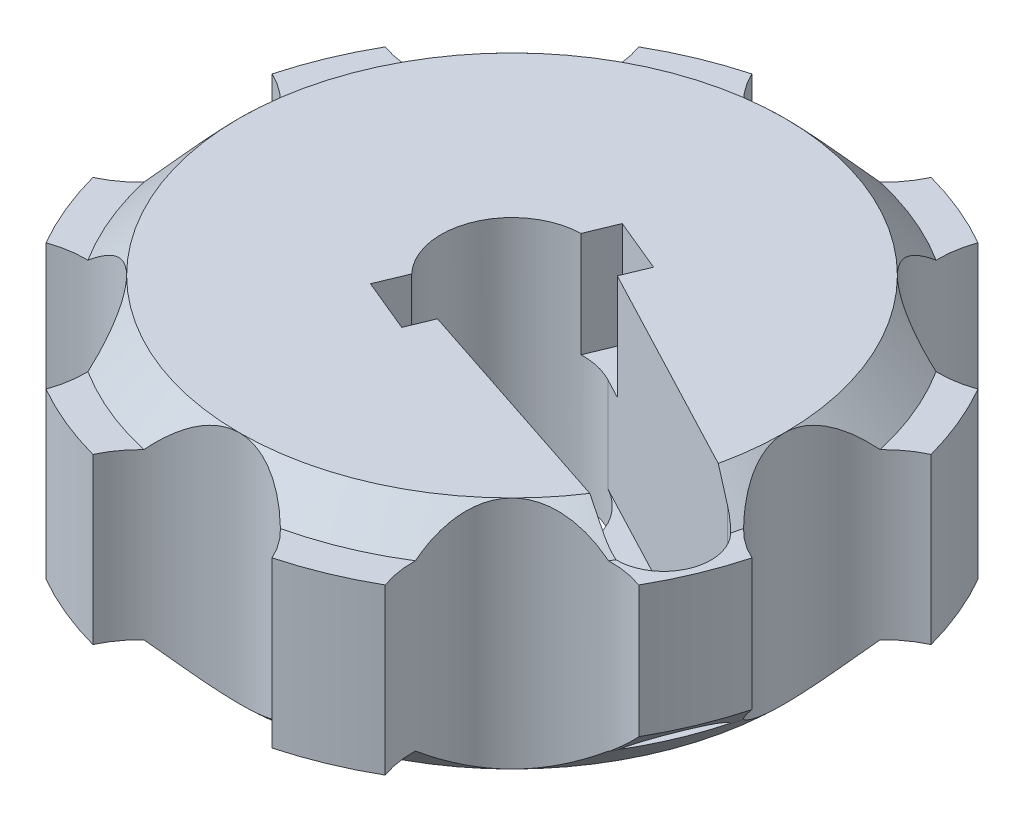
SolidWorks part; units mm, degrees
note: The reader was unsure of these and kept them because the rebuilt part matched: shared geometry of "Sketch1<4>", "Sketch1<5>", "Sketch2<3>".
ref_plane "Front Plane" through (0, 0, 0) normal (0, 0, 1) x (1, 0, 0)
ref_plane "Top Plane" through (0, 0, 0) normal (0, 1, 0) x (1, 0, 0)
ref_plane "Right Plane" through (0, 0, 0) normal (1, 0, 0) x (0, 0, -1)
sketch "Sketch1" plane through (0, 0, 0) normal (0, 1, 0) x (1, 0, 0)
  line L0 (0, -21.2055) -> (21.2055, -21.2055) construction
  line L1 (0, -21.2055) -> (14.9946, -14.9946) construction
  line L2 (14.9946, -14.9946) -> (21.2055, 0) construction
  line L3 (21.2055, 0) -> (14.9946, 14.9946) construction
  line L4 (14.9946, 14.9946) -> (0, 21.2055) construction
  line L5 (0, 21.2055) -> (-14.9946, 14.9946) construction
  line L6 (-14.9946, 14.9946) -> (-21.2055, 0) construction
  line L7 (-21.2055, 0) -> (-14.9946, -14.9946) construction
  line L8 (-14.9946, -14.9946) -> (0, -21.2055) construction
  line L9 (21.2055, -21.2055) -> (21.2055, 0) construction
  arc A1 (5.1161, -18.8079) -> (-5.1161, -18.8079) centre (0, -21.2055) ccw
  arc A2 (-9.6816, -16.9168) -> (-16.9168, -9.6816) centre (-14.9946, -14.9946) ccw
  arc A3 (-18.8079, -5.1161) -> (-18.8079, 5.1161) centre (-21.2055, 0) ccw
  arc A4 (-16.9168, 9.6816) -> (-9.6816, 16.9168) centre (-14.9946, 14.9946) ccw
  arc A5 (-5.1161, 18.8079) -> (5.1161, 18.8079) centre (0, 21.2055) ccw
  arc A6 (9.6816, 16.9168) -> (16.9168, 9.6816) centre (14.9946, 14.9946) ccw
  arc A7 (-9.6816, -16.9168) -> (-5.1161, -18.8079) centre (0, 0) ccw
  arc A8 (-16.9168, -9.6816) -> (-18.8079, -5.1161) centre (0, 0) cw
  arc A9 (-18.8079, 5.1161) -> (-16.9168, 9.6816) centre (0, 0) cw
  arc A10 (-9.6816, 16.9168) -> (-5.1161, 18.8079) centre (0, 0) cw
  arc A11 (5.1161, 18.8079) -> (9.6816, 16.9168) centre (0, 0) cw
  arc A13 (18.8079, 5.1161) -> (18.8079, -5.1161) centre (21.2055, 0) ccw
  arc A14 (16.9168, -9.6816) -> (9.6816, -16.9168) centre (14.9946, -14.9946) ccw
  arc A15 (5.1161, -18.8079) -> (9.6816, -16.9168) centre (0, 0) ccw
  arc A16 (16.9168, -9.6816) -> (18.8079, -5.1161) centre (0, 0) ccw
  arc A17 (18.8079, 5.1161) -> (16.9168, 9.6816) centre (0, 0) ccw
  circle A18 centre (0, 0) radius 19.5913 construction
  circle A19 centre (0, 0) radius 15.5555
  point P23 (0, 0)
  point P27 (-5.1161, -18.8079)
  point P29 (-5.1161, -18.8079)
  point P31 (-7.459, -18.0077)
  point P33 (-7.4973, -18.1)
  point P37 (-9.6816, -16.9168)
  dimension "D1" = 16.23
  dimension "D2" = 0.1
  dimension "D3" = 5.65
  dimension "D4" = 8
extrude "Boss-Extrude1" add sketch "Sketch1" along normal blind 9.4 contours A19 A3 A8 A2 | A19 A2 A7 A1 | A19 A1 A15 A14 | A19 | A19 A14 A16 A13 | A19 A13 A17 A6 | A19 A6 A11 A5 | A19 A5 A10 A4 | A19 A4 A9 A3
extrude "Boss-Extrude2" add sketch "Sketch1<4>" along normal blind 2 from surface at 9.4 contours A19 starting at face at (0, 9.4, 0)
sketch "Sketch1<4>" plane through (0, 0, 0) normal (0, 1, 0) x (1, 0, 0) same geometry as "Sketch1"
extrude "Boss-Extrude3" add sketch "Sketch1<5>" against normal blind 2 from surface at 0 contours A19 starting at face at (0, 0, 0)
sketch "Sketch1<5>" plane through (0, 0, 0) normal (0, 1, 0) x (1, 0, 0) same geometry as "Sketch1"
chamfer "Chamfer2" distance 2 angle 45 16 edges at (-5.9528, 9.4, 14.3714) (-14.3714, 9.4, 5.9528) (-14.3714, 9.4, -5.9528) (-5.9528, 9.4, -14.3714) (5.9528, 9.4, -14.3714) (14.3714, 9.4, -5.9528) (14.3714, 9.4, 5.9528) (5.9528, 9.4, 14.3714) (-5.9528, 0, 14.3714) (-14.3714, 0, 5.9528) (-14.3714, 0, -5.9528) (-5.9528, 0, -14.3714) (5.9528, 0, -14.3714) (14.3714, 0, -5.9528) (14.3714, 0, 5.9528) (5.9528, 0, 14.3714)
sketch "Sketch2" plane through (0, 11.4, 0) normal (0, 1, 0) x (1, 0, 0)
  line L0 (-1.1752, -3.5611) -> (14.2981, -8.6676) construction
  line L1 (1.7453, 3.3191) -> (16.1672, -4.2642) construction
  line L2 (0, 0) -> (15.5555, 0) construction
  line L3 (0, 0) -> (15.0503, -6.3885) construction
  line L4 (-1.2692, -3.846) -> (14.2041, -8.9524)
  line L5 (1.8849, 3.5847) -> (16.3068, -3.9987)
  arc A0 (1.7453, 3.3191) -> (-1.1752, -3.5611) centre (0, 0) ccw construction
  arc A3 (16.1672, -4.2642) -> (14.2981, -8.6676) centre (15.0503, -6.3885) cw construction
  arc A4 (-1.1752, -3.5611) -> (1.7453, 3.3191) centre (0, 0) ccw construction
  arc A5 (-1.2692, -3.846) -> (1.8849, 3.5847) centre (0, 0) ccw
  arc A6 (1.8849, 3.5847) -> (-1.2692, -3.846) centre (0, 0) ccw
  arc A7 (16.3068, -3.9987) -> (14.2041, -8.9524) centre (15.0503, -6.3885) cw
  point P14 (0.6561, -0.2785)
  dimension "D2" = 2.4
  dimension "D5" = 0.3
  dimension "D1" = 7.5
  dimension "D3" = 16.35
  dimension "D4" = 23
extrude "Cut-Extrude1" cut sketch "Sketch2" against normal offset from surface (11.4 mm away) 2
extrude "Cut-Extrude2" cut sketch "Sketch2<3>" against normal up to surface (13.4 mm away) contours A5 A6 up to face at (0, -2, 0)
sketch "Sketch2<3>" plane through (0, 11.4, 0) normal (0, 1, 0) x (1, 0, 0) same geometry as "Sketch2"
sketch "Shaft Key" plane through (0, 11.4, 0) normal (0, 1, 0) x (1, 0, 0)
  line L0 (0.6935, -2.2453) -> (-0.6615, -5.5168) construction
  line L7 (-0.6615, -5.5168) -> (-3.4332, -4.3687) construction
  line L8 (-3.4332, -4.3687) -> (-2.0781, -1.0973) construction
  line L9 (-0.8993, -2.1711) -> (-2.0474, -4.9428) construction
  line L10 (-2.1711, 0.8993) -> (2.1711, -0.8993) construction
  line L11 (0.6615, 5.5168) -> (-0.6935, 2.2453) construction
  line L12 (3.4332, 4.3687) -> (0.6615, 5.5168) construction
  line L13 (2.0781, 1.0973) -> (3.4332, 4.3687) construction
  line L14 (0, 0) -> (-0.8993, -2.1711) construction
  line L15 (0.8057, -2.3666) -> (-0.5804, -5.7128)
  line L16 (-0.5804, -5.7128) -> (-3.6292, -4.4499)
  line L17 (-3.6292, -4.4499) -> (-2.2431, -1.1038)
  line L18 (0.5804, 5.7128) -> (-0.8057, 2.3666)
  line L19 (3.6292, 4.4499) -> (0.5804, 5.7128)
  line L20 (2.2431, 1.1038) -> (3.6292, 4.4499)
  line L21 (-5.9528, -14.3714) -> (-2.0474, -4.9428) construction
  arc A0 (0.6935, -2.2453) -> (2.0781, 1.0973) centre (0, 0) ccw construction
  arc A1 (-2.0781, -1.0973) -> (-0.8993, -2.1711) centre (0, 0) ccw construction
  arc A2 (-0.8993, -2.1711) -> (0.6935, -2.2453) centre (0, 0) ccw construction
  arc A3 (-0.6935, 2.2453) -> (-2.0781, -1.0973) centre (0, 0) ccw construction
  arc A4 (2.0781, 1.0973) -> (-0.6935, 2.2453) centre (0, 0) ccw construction
  arc A5 (-0.8057, 2.3666) -> (-2.2431, -1.1038) centre (0, 0) ccw
  arc A6 (0.8057, -2.3666) -> (2.2431, 1.1038) centre (0, 0) ccw
  arc A8 (-10.9994, -10.9994) -> (0, -15.5555) centre (0, 0) ccw construction
  point P11 (0, 0)
  dimension "D1" = 4.7
  dimension "D2" = 3
  dimension "D3" = 3
  dimension "D4" = 0.15
extrude "Key-Cut" cut sketch "Shaft Key" against normal blind 6
chamfer "Chamfer3" distance 1.9 angle 45 1 edges at (18.0077, 0, 7.459)
equation "\"KeyDepth\"= 6"
equation "\"D1@Key-Cut\"=\"KeyDepth\""
